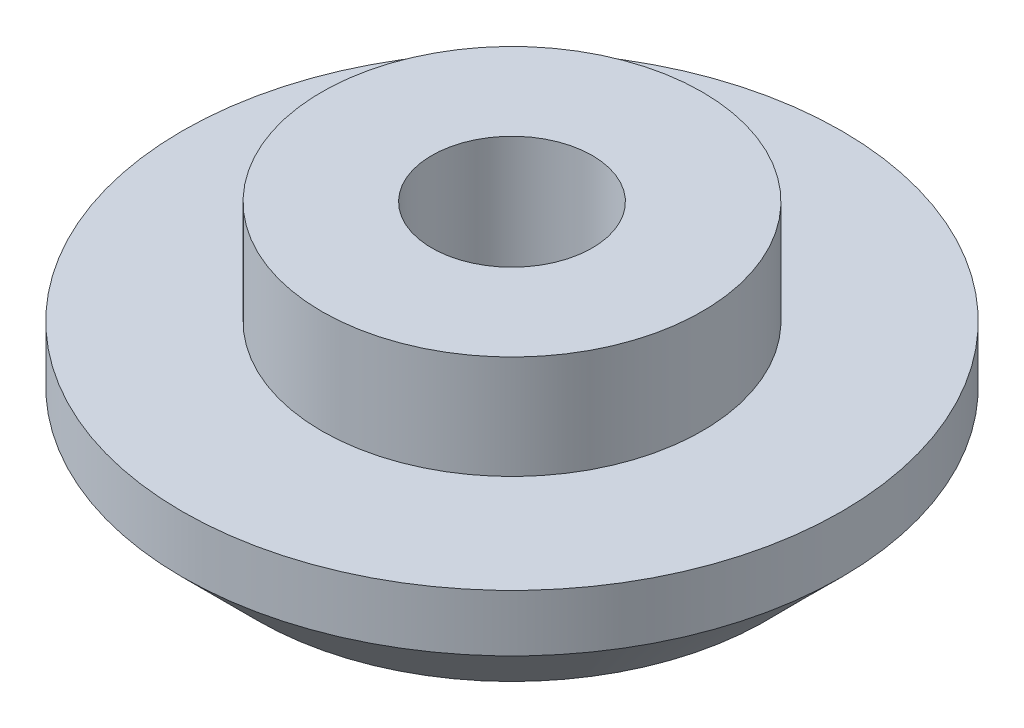
SolidWorks part; units mm, degrees
ref_plane "Front Plane" through (0, 0, 0) normal (0, 0, 1) x (1, 0, 0)
ref_plane "Top Plane" through (0, 0, 0) normal (0, 1, 0) x (1, 0, 0)
ref_plane "Right Plane" through (0, 0, 0) normal (1, 0, 0) x (0, 0, -1)
sketch "Sketch1" plane through (0, 0, 0) normal (0, 0, 1) x (1, 0, 0)
  line L0 (0, 0) -> (2.75, 0) construction
  line L1 (0, 1.7014) -> (4.1104, 1.7014) construction
  line L2 (0, 0.6) -> (2.75, 0.6)
  line L3 (2.75, 0.6) -> (2.75, 0)
  line L4 (0, 4.41) -> (3.556, 4.41)
  line L5 (2.75, 0) -> (4.75, 0)
  line L6 (4.75, 0) -> (6.1642, 1.4142)
  line L7 (6.1642, 1.4142) -> (6.1642, 2.4754)
  line L8 (0, 4.41) -> (0, 0.6)
  line L9 (3.556, 4.41) -> (3.556, 2.4754)
  line L10 (3.556, 2.4754) -> (6.1642, 2.4754)
  dimension "D1" = 2.75
  dimension "D2" = 0.6
  dimension "D3" = 3.556
  dimension "D4" = 135
  dimension "D5" = 3.81
  dimension "D6" = 2
revolve "Revolve1" add sketch "Sketch1" angle 360 about L8
sketch "Sketch2" plane through (0, 0.6, 0) normal (0, -1, 0) x (1, 0, 0)
  circle A0 centre (0, 0) radius 1.5
  dimension "D1" = 3
extrude "Cut-Extrude1" cut sketch "Sketch2" against normal through all
